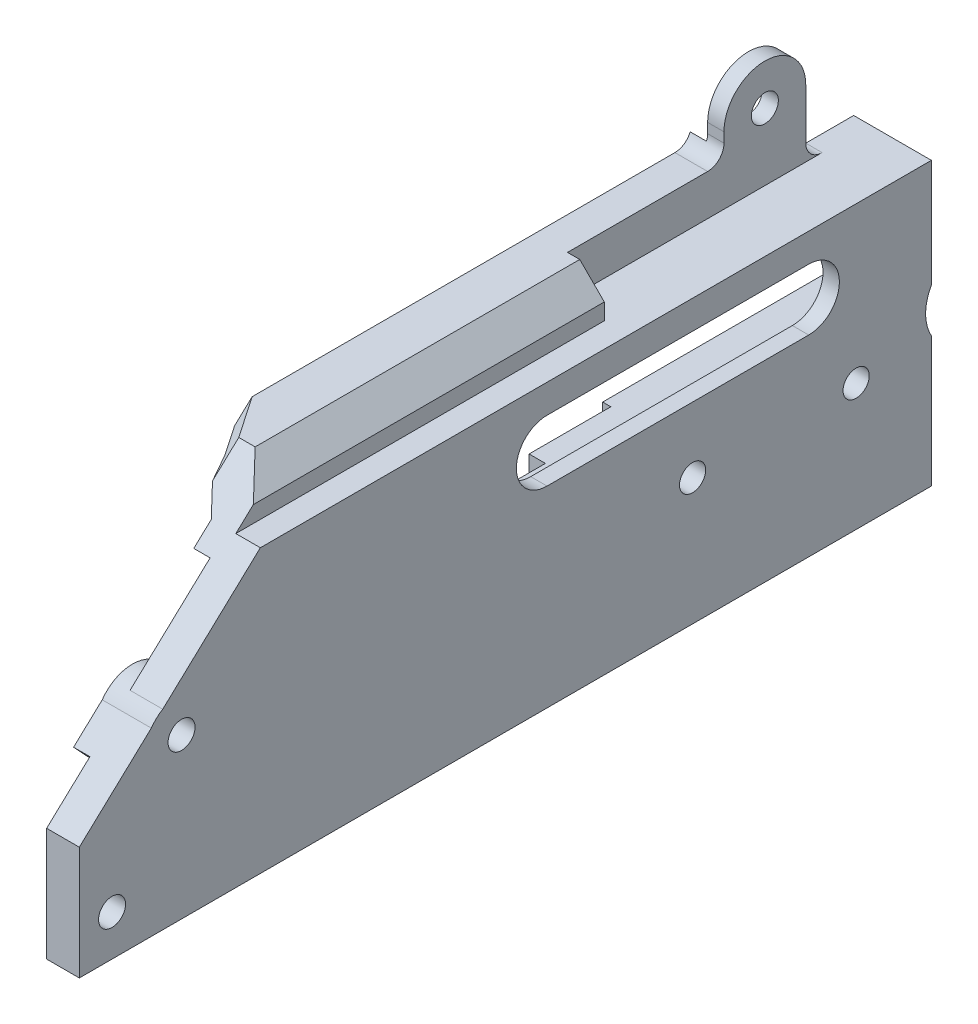
SolidWorks part; units mm, degrees
ref_plane "前视基准面" through (0, 0, 0) normal (0, 0, 1) x (1, 0, 0)
ref_plane "上视基准面" through (0, 0, 0) normal (0, 1, 0) x (1, 0, 0)
ref_plane "右视基准面" through (0, 0, 0) normal (1, 0, 0) x (0, 0, -1)
other "Configuration Table"
sketch "草图1" plane through (0, 0, 0) normal (1, 0, 0) x (0, 0, -1)
  line L0 (0, 0) -> (20, 0) construction
  line L2 (29.2, 6.5) -> (-4, 6.5)
  line L3 (29.2, 6.5) -> (29.2, -15.5)
  line L4 (29.2, -15.5) -> (-4, -15.5)
  line L5 (-4, 6.5) -> (-4, -15.5)
  circle A0 centre (0, 0) radius 1.6
  circle A1 centre (20, 0) radius 1.6
  dimension "D1" = 20
  dimension "D2" = 3.2
  dimension "D4" = 9.2
  dimension "D6" = 4
  dimension "D3" = 6.5
  dimension "D5" = 22
extrude "凸台-拉伸1" add sketch "草图1" along normal blind 7
sketch "草图2" plane through (7, 0, 0) normal (1, 0, 0) x (0, 0, -1)
  line L1 (-4, 6.5) -> (29.2, 6.5)
  line L2 (-4, 6.5) -> (-4, 17)
  line L3 (-4, 17) -> (29.2, 17)
  line L4 (29.2, 6.5) -> (29.2, 17)
  dimension "D1" = 10.5
extrude "凸台-拉伸2" add sketch "草图2" against normal offset from surface (2 mm away) 5 up to face at (0, 0, -1.6)
sketch "草图3" plane through (0, 0, 4) normal (0, 0, 1) x (1, 0, 0)
  line L1 (7, -15.5) -> (1, -15.5)
  line L2 (7, -15.5) -> (7, 6.5)
  line L3 (7, 6.5) -> (3, 6.5)
  line L4 (1, -15.5) -> (1, 4.5)
  line L5 (3, 6.5) -> (3, 4.5)
  line L6 (3, 4.5) -> (1, 4.5)
  line L7 (5, 6.5) -> (0, 6.5) construction
  dimension "D1" = 6
  dimension "D2" = 2
  dimension "D3" = 2
extrude "凸台-拉伸3" add sketch "草图3" along normal blind 60
sketch "草图4" plane through (0, 0, 4) normal (0, 0, 1) x (1, 0, 0)
  line L4 (5, 6.5) -> (7, 6.5)
  line L5 (7, 6.5) -> (7, 17)
  line L6 (7, 17) -> (5, 17)
  line L7 (5, 17) -> (5, 6.5)
  line L8 (5, 6.5) -> (7, 6.5)
  line L9 (7, 6.5) -> (7, 17)
  line L10 (7, 17) -> (5, 17)
  line L11 (5, 17) -> (5, 6.5)
  dimension "D1" = 0
extrude "凸台-拉伸4" add sketch "草图4" along normal blind 38.5
sketch "草图5" plane through (0, 0, 42.5) normal (0, 0, 1) x (1, 0, 0)
  line L0 (7, 6.5) -> (7, 17) construction
  line L1 (7, 6.5) -> (3, 6.5)
  line L2 (7, 6.5) -> (7, 17)
  line L3 (7, 17) -> (3, 17)
  line L4 (3, 6.5) -> (3, 17)
  line L5 (7, 17) -> (5, 17) construction
extrude "凸台-拉伸5" add sketch "草图5" along normal blind 2
sketch "草图6" plane through (0, 0, 44.5) normal (0, 0, 1) x (1, 0, 0)
  line L4 (7, 6.5) -> (7, 17)
  line L5 (7, 17) -> (3, 17)
  line L6 (3, 17) -> (3, 6.5)
  line L7 (3, 6.5) -> (7, 6.5)
  line L8 (7, 6.5) -> (7, 17)
  line L9 (7, 17) -> (3, 17)
  line L10 (3, 17) -> (3, 6.5)
  line L11 (3, 6.5) -> (7, 6.5)
  dimension "D1" = 0
extrude "凸台-拉伸6" add sketch "草图6" along normal up to surface (19.5 mm away) up to face at (3.6667, -1.5, 64)
sketch "草图7" plane through (0, 17, 0) normal (0, 1, 0) x (1, 0, 0)
  line L0 (1, -64) -> (1, -4) construction
  line L1 (7, 29.2) -> (1, 29.2)
  line L2 (7, 29.2) -> (7, -64)
  line L3 (7, -64) -> (1, -64)
  line L4 (1, 29.2) -> (1, -64)
  line L5 (7, -64) -> (3, -64) construction
extrude "凸台-拉伸7" add sketch "草图7" along normal blind 2
sketch "草图8" plane through (1, 0, 0) normal (-1, 0, 0) x (0, 0, 1)
  line L1 (-29.2, 19) -> (64, 19)
  line L2 (-29.2, 19) -> (-29.2, 24)
  line L3 (-29.2, 24) -> (64, 24)
  line L4 (64, 19) -> (64, 24)
  dimension "D1" = 5
extrude "凸台-拉伸8" add sketch "草图8" against normal blind 3
sketch "草图10" plane through (1, 0, 0) normal (-1, 0, 0) x (0, 0, 1)
  line L1 (-29.2, 24) -> (64, 24)
  line L2 (-29.2, 24) -> (-29.2, 22)
  line L3 (-29.2, 22) -> (64, 22)
  line L4 (64, 24) -> (64, 22)
  line L5 (64, 24) -> (64, 17) construction
  dimension "D1" = 2
extrude "凸台-拉伸9" add sketch "草图10" along normal blind 5.5
sketch "草图12" plane through (-4.5, 0, 0) normal (-1, 0, 0) x (0, 0, 1)
  line L0 (64, 24) -> (-29.2, 24) construction
  line L1 (-29.2, 22) -> (-11.2, 22)
  line L2 (-29.2, 22) -> (-29.2, 24)
  line L3 (-29.2, 24) -> (-11.2, 24)
  line L4 (-11.2, 22) -> (-11.2, 24)
  dimension "D1" = 18
extrude "切除-拉伸1" cut sketch "草图12" against normal up to surface (5.5 mm away) up to face at (1, 19.5, 17.4)
sketch "草图13" plane through (1, 0, 0) normal (-1, 0, 0) x (0, 0, 1)
  line L0 (-11.2, 22) -> (64, 22) construction
  line L1 (10.8, 22) -> (-29.2, 22)
  line L2 (10.8, 22) -> (10.8, 17)
  line L3 (10.8, 17) -> (-29.2, 17)
  line L4 (-29.2, 22) -> (-29.2, 17)
  dimension "D1" = 40
extrude "凸台-拉伸10" add sketch "草图13" along normal blind 3.5
sketch "草图14" plane through (-2.5, 0, 0) normal (-1, 0, 0) x (0, 0, 1)
  line L0 (-29.2, 17) -> (10.8, 17) construction
  line L1 (-11.2, 19.8) -> (-9.2, 19.8)
  line L2 (-11.2, 19.8) -> (-11.2, 17)
  line L3 (-11.2, 17) -> (-9.2, 17)
  line L4 (-9.2, 19.8) -> (-9.2, 17)
  line L5 (10.8, 22) -> (-11.2, 22) construction
  line L6 (-11.2, 22) -> (-11.2, 24) construction
  dimension "D1" = 2
  dimension "D2" = 2.2
sketch "草图15" plane through (4, 0, 0) normal (1, 0, 0) x (0, 0, -1)
  line L0 (29.2, 19) -> (-64, 19) construction
  line L1 (29.2, 24) -> (13.7, 24)
  line L2 (29.2, 24) -> (29.2, 19)
  line L3 (29.2, 19) -> (13.7, 19)
  line L4 (13.7, 24) -> (13.7, 19)
  line L6 (11.2, 22) -> (11.2, 24) construction
  dimension "D1" = 2.5
extrude "切除-拉伸2" cut sketch "草图15" against normal up to next
sketch "草图16" plane through (0, 22, 0) normal (0, 1, 0) x (1, 0, 0)
  line L4 (1, 11.2) -> (1, 13.7)
  line L5 (1, 13.7) -> (-2.5, 13.7)
  line L6 (-2.5, 13.7) -> (-2.5, 11.2)
  line L7 (-2.5, 11.2) -> (1, 11.2)
  line L8 (1, 11.2) -> (1, 13.7)
  line L9 (1, 13.7) -> (-2.5, 13.7)
  line L10 (-2.5, 13.7) -> (-2.5, 11.2)
  line L11 (-2.5, 11.2) -> (1, 11.2)
  dimension "D1" = 0
extrude "凸台-拉伸12" add sketch "草图16" along normal up to surface (2 mm away) up to face at (0.1667, 24, 13.0333)
sketch "草图17" plane through (7, 0, 0) normal (1, 0, 0) x (0, 0, -1)
  line L0 (-47.5, 24) -> (-64, 8.6135)
  line L1 (-64, 24) -> (13.7, 24) construction
  line L2 (-64, -15.5) -> (-64, 19) construction
  line L3 (-64, 8.6135) -> (-64, 24)
  line L4 (-64, 24) -> (-47.5, 24)
  dimension "D1" = 133
  dimension "D2" = 16.5
extrude "切除-拉伸3" cut sketch "草图17" against normal up to next
chamfer "倒角1" distance 3.5 angle 45 1 edges at (-4.5, 23, 48.5724)
sketch "草图18" plane through (-2.5, 0, 0) normal (-1, 0, 0) x (0, 0, 1)
  line L0 (-13.7, 19) -> (-13.7, 24) construction
  line L1 (-29.2, 19) -> (-13.7, 19) construction
  line L2 (-11.337, 27.2) -> (-11.337, 24)
  line L3 (-13.7, 24) -> (-11.2, 24) construction
  line L4 (-11.337, 24) -> (-13.7, 24)
  line L5 (-13.7, 24) -> (-13.7, 19)
  line L6 (-13.7, 19) -> (-21.337, 19)
  line L7 (-21.337, 19) -> (-21.337, 27.2)
  circle A0 centre (-16.337, 27.2) radius 1.65
  arc A1 (-11.337, 27.2) -> (-21.337, 27.2) centre (-16.337, 27.2) ccw
  dimension "D1" = 2.637
  dimension "D2" = 8.2
  dimension "D3" = 3.3
  dimension "D4" = 10
extrude "凸台-拉伸13" add sketch "草图18" against normal blind 2
fillet "圆角1" radius 2 2 edges at (-1.5, 24, -11.337) (-1.5, 19, -21.337)
sketch "草图19" plane through (0, 24, 0) normal (0, 1, 0) x (1, 0, 0)
  line L0 (-0.5, 9.337) -> (-0.5, 11.337) construction
  line L1 (4, 13.7) -> (-0.5, 13.7)
  line L2 (4, 13.7) -> (4, -7.8)
  line L3 (4, -7.8) -> (-0.5, -7.8)
  line L4 (-0.5, 13.7) -> (-0.5, -7.8)
  line L5 (-2.5, -10.8) -> (1, -10.8) construction
  dimension "D1" = 3
extrude "切除-拉伸4" cut sketch "草图19" against normal up to surface (5 mm away) up to face at (2, 19, -3.3438)
chamfer "倒角2" distance 3 angle 45 2 edges at (4, 24, 27.65) (1, 22, 30.2224)
sketch "草图20" plane through (7, 0, 0) normal (1, 0, 0) x (0, 0, -1)
  line L0 (-64, -15.5) -> (-64, 8.6135) construction
  line L1 (-64, -15.5) -> (29.2, -15.5) construction
  circle A0 centre (-62.5, 4) radius 1.65
  dimension "D1" = 1.5
  dimension "D2" = 19.5
  dimension "D3" = 3.3
extrude "切除-拉伸5" cut sketch "草图20" against normal up to next
sketch "草图21" plane through (1, 0, 0) normal (-1, 0, 0) x (0, 0, 1)
  circle A0 centre (62.5, 4) radius 1.65
  circle A1 centre (62.5, 4) radius 4.5
  dimension "D1" = 9
extrude "凸台-拉伸14" add sketch "草图21" against normal up to surface (6 mm away) up to face at (7, 3.3734, 35.3303)
sketch "草图22" plane through (1, 0, 0) normal (-1, 0, 0) x (0, 0, 1)
  line L3 (66.1986, 6.5633) -> (75, -1.6442)
  line L4 (75, -1.6442) -> (75, -15.5)
  line L5 (75, -15.5) -> (64, -15.5)
  line L6 (55.0066, 17) -> (64, 8.6135) construction
  line L7 (64, -0.2426) -> (64, -15.5)
  circle A2 centre (62.5, 4) radius 1.65 construction
  arc A3 (64, -0.2426) -> (58.0279, 4.5) centre (62.5, 4) ccw construction
  arc A4 (64, -0.2426) -> (66.1986, 6.5633) centre (62.5, 4) ccw
  dimension "D1" = 12.5
extrude "凸台-拉伸15" add sketch "草图22" against normal up to surface (6 mm away) up to face at (7, 3.3734, 36.2088)
sketch "草图23" plane through (7, 0, 0) normal (1, 0, 0) x (0, 0, -1)
  line L0 (-64, 8.6135) -> (-64.799, 7.8684)
  line L1 (-64.799, 7.8684) -> (-64, 8.2426)
  line L2 (-64, 8.2426) -> (-64, 8.6135)
  line L3 (-64, 8.6135) -> (-52.8618, 19) construction
  arc A0 (-64, 8.2426) -> (-66.1986, 6.5633) centre (-62.5, 4) ccw construction
extrude "凸台-拉伸16" add sketch "草图23" against normal up to surface (4 mm away) up to face at (3, 9.2872, 41.6414)
sketch "草图24" plane through (1, 0, 0) normal (-1, 0, 0) x (0, 0, 1)
  line L0 (75, -15.5) -> (75, -1.6442) construction
  line L1 (75, -15.5) -> (4, -15.5) construction
  circle A0 centre (71, -10.5) radius 1.65
  dimension "D1" = 3.3
  dimension "D2" = 4
  dimension "D3" = 5
extrude "切除-拉伸6" cut sketch "草图24" against normal up to next
sketch "草图25" plane through (5, 0, 0) normal (-1, 0, 0) x (0, 0, 1)
  line L0 (-29.2, 11.75) -> (42.5, 11.75) construction
  line L1 (-29.2, 6.5) -> (-29.2, 17) construction
  line L2 (42.5, 17) -> (42.5, 6.5) construction
  line L3 (17.8, 11.75) -> (-14.2, 11.75) construction
  line L4 (17.8, 8) -> (-14.2, 8)
  line L5 (17.8, 15.5) -> (-14.2, 15.5)
  arc A0 (17.8, 8) -> (17.8, 15.5) centre (17.8, 11.75) ccw
  arc A1 (-14.2, 15.5) -> (-14.2, 8) centre (-14.2, 11.75) ccw
  point P8 (1.8, 11.75)
  dimension "D1" = 47
  dimension "D2" = 15
  dimension "D3" = 7.5
extrude "切除-拉伸7" cut sketch "草图25" against normal up to next
sketch "草图26" plane through (0, 0, 42.5) normal (0, 0, -1) x (-1, 0, 0)
  line L4 (-5, 17) -> (-5, 6.5)
  line L5 (-5, 6.5) -> (-3, 6.5)
  line L6 (-3, 6.5) -> (-3, 17)
  line L7 (-3, 17) -> (-5, 17)
  line L8 (-5, 17) -> (-5, 6.5)
  line L9 (-5, 6.5) -> (-3, 6.5)
  line L10 (-3, 6.5) -> (-3, 17)
  line L11 (-3, 17) -> (-5, 17)
  dimension "D1" = 0
extrude "切除-拉伸8" cut sketch "草图26" against normal blind 5
sketch "草图27" plane through (0, 0, 4) normal (0, 0, 1) x (1, 0, 0)
  line L1 (1, 4.5) -> (3, 4.5)
  line L2 (1, 4.5) -> (1, 6.5)
  line L3 (1, 6.5) -> (3, 6.5)
  line L4 (3, 4.5) -> (3, 6.5)
extrude "凸台-拉伸17" add sketch "草图27" along normal blind 10
sketch "草图28" plane through (1, 0, 0) normal (-1, 0, 0) x (0, 0, 1)
  line L0 (67, 0.3946) -> (67, -15.5)
  line L2 (75, -15.5) -> (4, -15.5) construction
  line L3 (67, -15.5) -> (75, -15.5)
  line L4 (75, -15.5) -> (75, -1.6442)
  line L5 (75, -1.6442) -> (69.7041, 3.2943)
  line L6 (69.7041, 3.2943) -> (67, 0.3946)
  line L7 (75, -1.6442) -> (66.1986, 6.5633) construction
  circle A0 centre (62.5, 4) radius 1.65 construction
  point P0 (69.5213, 3.4648)
  dimension "D3" = 5.75
  dimension "D1" = 8
  dimension "D2" = 137
extrude "切除-拉伸9" cut sketch "草图28" against normal blind 2
sketch "草图29" plane through (7, 0, 0) normal (1, 0, 0) x (0, 0, -1)
  circle A0 centre (34, 3.1) radius 5.5
  circle A1 centre (20, 0) radius 1.6 construction
  dimension "D1" = 3.1
  dimension "D2" = 14
  dimension "D3" = 11
extrude "切除-拉伸10" cut sketch "草图29" against normal up to next
sketch "草图30" plane through (1, 0, 0) normal (-1, 0, 0) x (0, 0, 1)
  line L0 (4, 6.5) -> (4, -15.5) construction
  line L1 (4, -4.5) -> (67, -4.5)
  line L2 (4, -4.5) -> (4, -6.5)
  line L3 (4, -6.5) -> (67, -6.5)
  line L4 (67, -4.5) -> (67, -6.5)
  line L5 (67, 0.3946) -> (67, -15.5) construction
  circle A0 centre (0, 0) radius 1.6 construction
  dimension "D1" = 4.5
  dimension "D2" = 2
extrude "凸台-拉伸18" add sketch "草图30" along normal up to surface (1 mm away) up to face at (0, -1.9667, -18.0167)
